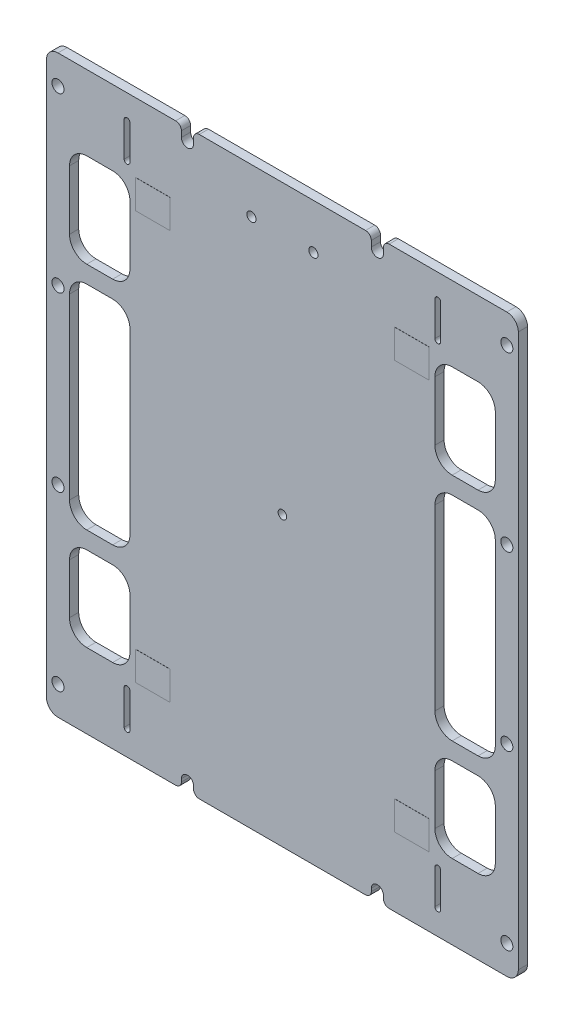
SolidWorks part; units mm, degrees
material "FR4_stuffedProtoboard"
ref_plane "Front Plane" through (0, 0, 0) normal (0, 0, 1) x (1, 0, 0)
ref_plane "Top Plane" through (0, 0, 0) normal (0, 1, 0) x (1, 0, 0)
ref_plane "Right Plane" through (0, 0, 0) normal (1, 0, 0) x (0, 0, -1)
sketch "Sketch1" plane through (0, 0, 0) normal (0, 0, 1) x (1, 0, 0)
  line L1 (-39, -50) -> (39, -50)
  line L2 (-41, -48) -> (-41, 48)
  line L3 (-39, 50) -> (39, 50)
  line L4 (41, -48) -> (41, 48)
  line L5 (-41, -50) -> (41, 50) construction
  line L6 (-41, 50) -> (41, -50) construction
  arc A0 (-39, -50) -> (-41, -48) centre (-39, -48) cw
  arc A1 (39, -50) -> (41, -48) centre (39, -48) ccw
  arc A2 (39, 50) -> (41, 48) centre (39, 48) cw
  arc A3 (-41, 48) -> (-39, 50) centre (-39, 48) cw
  point P0 (0, 0)
  dimension "D3" = 2
  dimension "D1" = 100
  dimension "D2" = 82
extrude "boardOutline" add sketch "Sketch1" along normal blind 1.6
sketch "Sketch2" plane through (0, 0, 1.6) normal (0, 0, 1) x (1, 0, 0)
  line L0 (39, 50) -> (-39, 50) construction
  line L1 (-41, 48) -> (-41, -48) construction
  line L3 (-37.5, 44.2) -> (-37.5, 4.2) construction
  circle A0 centre (0, 0) radius 0.75
  circle A1 centre (-37.5, 44.2) radius 1.05 construction
  circle A2 centre (37.5, 44.2) radius 1.05 construction
  circle A3 centre (37.5, 4.2) radius 1.05 construction
  circle A4 centre (37.5, -35.8) radius 1.05 construction
  circle A5 centre (-37.5, 4.2) radius 1.05 construction
  circle A6 centre (-37.5, -35.8) radius 1.05 construction
  circle A7 centre (-5.38, 42.15) radius 0.8
  circle A8 centre (5.39, 42.15) radius 0.8
  dimension "D1" = 1.5
  dimension "D2" = 2.1
  dimension "D9" = 10.77
  dimension "D7" = 1.6
  dimension "D11" = 7.85
  dimension "D12" = 35.62
  dimension "D3" = 5.8
  dimension "D4" = 3.5
  dimension "D8" = 40
  dimension "D10" = 37.5
  dimension "D5" = 2
  dimension "D6" = 3
extrude "componentHoles" cut sketch "Sketch2" against normal through all
sketch "Sketch4" plane through (0, 0, 1.6) normal (0, 0, 1) x (1, 0, 0)
  line L0 (-27, 39.75) -> (-27, 45.75) construction
  line L1 (-27.5, 39.75) -> (-27.5, 45.75)
  line L2 (-26.5, 39.75) -> (-26.5, 45.75)
  line L3 (39, 50) -> (-39, 50) construction
  line L4 (-41, 48) -> (-41, -48) construction
  line L5 (27, 39.75) -> (27, 45.75) construction
  line L6 (26.5, 39.75) -> (26.5, 45.75)
  line L7 (27.5, 39.75) -> (27.5, 45.75)
  line L8 (27, -45.75) -> (27, -39.75) construction
  line L9 (26.5, -45.75) -> (26.5, -39.75)
  line L10 (27.5, -45.75) -> (27.5, -39.75)
  line L11 (-27, -45.75) -> (-27, -39.75) construction
  line L12 (-27.5, -45.75) -> (-27.5, -39.75)
  line L13 (-26.5, -45.75) -> (-26.5, -39.75)
  line L14 (-27, 39.75) -> (27, 39.75) construction
  line L15 (-39, -50) -> (39, -50) construction
  arc A0 (-27.5, 39.75) -> (-26.5, 39.75) centre (-27, 39.75) ccw
  arc A1 (-26.5, 45.75) -> (-27.5, 45.75) centre (-27, 45.75) ccw
  arc A2 (26.5, 39.75) -> (27.5, 39.75) centre (27, 39.75) ccw
  arc A3 (27.5, 45.75) -> (26.5, 45.75) centre (27, 45.75) ccw
  arc A4 (26.5, -45.75) -> (27.5, -45.75) centre (27, -45.75) ccw
  arc A5 (27.5, -39.75) -> (26.5, -39.75) centre (27, -39.75) ccw
  arc A6 (-27.5, -45.75) -> (-26.5, -45.75) centre (-27, -45.75) ccw
  arc A7 (-26.5, -39.75) -> (-27.5, -39.75) centre (-27, -39.75) ccw
  point P2 (-27, 42.75)
  point P16 (27, 42.75)
  point P23 (27, -42.75)
  point P30 (-27, -42.75)
  dimension "D1" = 4.25
  dimension "D2" = 13.5
  dimension "D3" = 1
  dimension "D4" = 6
  dimension "D7" = 54
  dimension "D8" = 14
  dimension "D9" = 4.25
  dimension "D10" = 4.25
  dimension "D5" = 2
  dimension "D6" = 2
extrude "solarCellContactHoles" cut sketch "Sketch4" against normal blind 1.6
sketch "Sketch3" plane through (0, 0, 1.6) normal (0, 0, 1) x (1, 0, 0)
  line L1 (-34, 37) -> (-29.5, 37)
  line L2 (-37, 34) -> (-37, 23.7)
  line L3 (-34, 20.7) -> (-29.5, 20.7)
  line L4 (-26.5, 34) -> (-26.5, 23.7)
  line L5 (-41, 48) -> (-41, -48) construction
  line L6 (-29.5, -22.3) -> (-34, -22.3)
  line L9 (0, 50) -> (0, -50) construction
  line L10 (39, 50) -> (-39, 50) construction
  line L11 (-39, -50) -> (39, -50) construction
  line L12 (-26.5, -25.3) -> (-26.5, -34)
  line L13 (-29.5, -37) -> (-34, -37)
  line L14 (-37, -25.3) -> (-37, -34)
  line L19 (-29.5, -19.3) -> (-34, -19.3)
  line L25 (-26.5, -16.3) -> (-26.5, 14.7)
  line L26 (-29.5, 17.7) -> (-34, 17.7)
  line L27 (-37, -16.3) -> (-37, 14.7)
  arc A0 (-37, 23.7) -> (-34, 20.7) centre (-34, 23.7) ccw
  arc A1 (-29.5, 20.7) -> (-26.5, 23.7) centre (-29.5, 23.7) ccw
  arc A2 (-29.5, 37) -> (-26.5, 34) centre (-29.5, 34) cw
  arc A3 (-34, 37) -> (-37, 34) centre (-34, 34) ccw
  arc A4 (-29.5, -19.3) -> (-26.5, -16.3) centre (-29.5, -16.3) ccw
  arc A5 (-26.5, -34) -> (-29.5, -37) centre (-29.5, -34) cw
  arc A6 (-34, -37) -> (-37, -34) centre (-34, -34) cw
  arc A7 (-34, -22.3) -> (-37, -25.3) centre (-34, -25.3) ccw
  arc A8 (-29.5, -22.3) -> (-26.5, -25.3) centre (-29.5, -25.3) cw
  arc A17 (-34, -19.3) -> (-37, -16.3) centre (-34, -16.3) cw
  arc A18 (-34, 17.7) -> (-37, 14.7) centre (-34, 14.7) ccw
  arc A19 (-26.5, 14.7) -> (-29.5, 17.7) centre (-29.5, 14.7) ccw
  point P12 (-26.5, 20.7)
  point P15 (-26.5, 37)
  point P18 (-37, 37)
  dimension "D5" = 3
  dimension "D10" = 13
  dimension "D7" = 3
  dimension "D11" = 3
  dimension "D1" = 10.5
  dimension "D2" = 29.3
  dimension "D3" = 13
  dimension "D4" = 4
  dimension "D8" = 3
  dimension "D9" = 3
  dimension "D6" = 37
extrude "windows_1side" cut sketch "Sketch3" against normal through all
sketch "Sketch5" plane through (0, 0, 1.6) normal (0, 0, 1) x (1, 0, 0)
  line L0 (-41, 48) -> (-41, -48) construction
  line L1 (-25.5, 38) -> (-19.5, 38)
  line L2 (-25.5, 38) -> (-25.5, 33)
  line L3 (-25.5, 33) -> (-19.5, 33)
  line L4 (-19.5, 38) -> (-19.5, 33)
  line L5 (39, 50) -> (-39, 50) construction
  line L6 (19.5, 38) -> (19.5, 33)
  line L7 (25.5, 38) -> (25.5, 33)
  line L8 (19.5, 33) -> (25.5, 33)
  line L9 (19.5, 38) -> (25.5, 38)
  line L10 (19.5, -33) -> (19.5, -38)
  line L11 (25.5, -33) -> (25.5, -38)
  line L12 (19.5, -38) -> (25.5, -38)
  line L13 (19.5, -33) -> (25.5, -33)
  line L14 (-25.5, -33) -> (-25.5, -38)
  line L15 (-19.5, -33) -> (-19.5, -38)
  line L16 (-25.5, -38) -> (-19.5, -38)
  line L17 (-25.5, -33) -> (-19.5, -33)
  line L18 (-25.5, 38) -> (19.5, 38) construction
  line L19 (-25.5, 38) -> (-25.5, -33) construction
  dimension "D1" = 5
  dimension "D2" = 6
  dimension "D3" = 15.5
  dimension "D4" = 12
  dimension "D7" = 45
  dimension "D8" = 71
  dimension "D5" = 2
  dimension "D6" = 2
extrude "contactPads" add sketch "Sketch5" along normal blind 0.02
hole_wizard "M2 Clearance Hole1" positions "Sketch6" profile "Sketch7" hole size "M2" standard "ANSI Metric" end condition through all
sketch "Sketch6" plane through (0, 0, 0) normal (0, 0, -1) x (-1, 0, 0)
  line L5 (39, -50) -> (39, -45) construction
  line L6 (39, -50) -> (-39, -50) construction
  line L7 (39, -45) -> (39, -15) construction
  line L8 (39, -15) -> (39, 15) construction
  line L9 (39, 15) -> (39, 45) construction
  line L10 (39, 45) -> (39, 50) construction
  line L11 (-39, 50) -> (39, 50) construction
  line L15 (37, -27.0602) -> (41, -27.0602) construction
  line L16 (37, -25.3) -> (37, -34) construction
  line L17 (41, 48) -> (41, -48) construction
  point P0 (39, 45)
  point P27 (39, -15)
  point P36 (39, -45)
  point P38 (39, 15)
  point P73 (39, -27.0602)
  dimension "D2" = 5
sketch "Sketch7" plane through (-39, 45, 0) normal (1, 0, 0) x (0, 1, 0)
  line L0 (0, 0) -> (0, 1.62)
  line L1 (0, 1.62) -> (1.05, 1.62)
  line L2 (1.05, 1.62) -> (1.05, 0)
  line L5 (1.05, 0) -> (0, 0)
  line L11 (0, -6.35) -> (0, 107.95) construction
  dimension "Thru Hole Dia." = 2.1
  dimension "Thru Hole Depth" = 1.62
sketch "Sketch10" plane through (0, 0, 0) normal (0, 0, -1) x (-1, 0, 0)
  line L0 (16.5, 48) -> (16.5, 55.0732) construction
  line L1 (15.45, 48) -> (15.45, 55.0732)
  line L2 (17.55, 48) -> (17.55, 55.0732)
  line L3 (16.5, -48.5) -> (16.5, -55.5732) construction
  line L4 (17.55, -48.5) -> (17.55, -55.5732)
  line L5 (15.45, -48.5) -> (15.45, -55.5732)
  line L6 (41, 48) -> (41, -48) construction
  line L8 (39, -50) -> (-39, -50) construction
  line L9 (-39, 50) -> (39, 50) construction
  arc A0 (15.45, 48) -> (17.55, 48) centre (16.5, 48) ccw
  arc A1 (17.55, 55.0732) -> (15.45, 55.0732) centre (16.5, 55.0732) ccw
  arc A2 (17.55, -48.5) -> (15.45, -48.5) centre (16.5, -48.5) ccw
  arc A3 (15.45, -55.5732) -> (17.55, -55.5732) centre (16.5, -55.5732) ccw
  point P2 (16.5, 51.5366)
  point P7 (16.5, -52.0366)
  dimension "D1" = 1.05
  dimension "D2" = 24.5
  dimension "D3" = 2
  dimension "D4" = 1.5
extrude "Cut-Extrude1" cut sketch "Sketch10" against normal through all both and the other way through all
fillet "Fillet3" radius 1 4 edges at (-17.55, 50, 0.8) (-15.45, 50, 0.8) (-15.45, -50, 0.8) (-17.55, -50, 0.8)
mirror "Mirror1" about plane through (0, 0, 0) normal (1, 0, 0) of "Cut-Extrude1", "Fillet3", "windows_1side", "M2 Clearance Hole1"
sketch "thermalContact" plane through (0, 0, 1.6) normal (0, 0, 1) x (1, 0, 0)
  line L0 (-37, 43) -> (-37, 23.7) construction
  line L1 (-34, 20.7) -> (-21, 20.7) construction
  line L2 (-18, 23.7) -> (-18, 43) construction
  line L3 (-21, 46) -> (-34, 46) construction
  line L4 (-41, 48) -> (-41, -162)
  line L5 (39, 50) -> (-39, 50)
  line L6 (41, -162) -> (41, 48)
  line L7 (-39, -164) -> (39, -164)
  line L8 (-41, 48) -> (-41, -162)
  line L9 (39, 50) -> (-39, 50)
  line L10 (41, -162) -> (41, 48)
  line L11 (-39, -164) -> (39, -164)
  line L12 (-37, 43) -> (-37, 23.7)
  line L13 (-34, 20.7) -> (-21, 20.7)
  line L14 (-18, 23.7) -> (-18, 43)
  line L15 (-21, 46) -> (-34, 46)
  line L16 (18, 43) -> (18, 23.7) construction
  line L17 (21, 20.7) -> (34, 20.7) construction
  line L18 (37, 23.7) -> (37, 43) construction
  line L19 (34, 46) -> (21, 46) construction
  line L20 (18, 43) -> (18, 23.7)
  line L21 (21, 20.7) -> (34, 20.7)
  line L22 (37, 23.7) -> (37, 43)
  line L23 (34, 46) -> (21, 46)
  line L24 (-12, -47) -> (12, -47) construction
  line L25 (15, -44) -> (15, -25.3) construction
  line L26 (12, -22.3) -> (-12, -22.3) construction
  line L27 (-15, -25.3) -> (-15, -44) construction
  line L28 (-12, -47) -> (12, -47)
  line L29 (15, -44) -> (15, -25.3)
  line L30 (12, -22.3) -> (-12, -22.3)
  line L31 (-15, -25.3) -> (-15, -44)
  line L32 (-37, -25.3) -> (-37, -44) construction
  line L33 (-34, -47) -> (-21, -47) construction
  line L34 (-18, -44) -> (-18, -25.3) construction
  line L35 (-21, -22.3) -> (-34, -22.3) construction
  line L36 (-37, -25.3) -> (-37, -44)
  line L37 (-34, -47) -> (-21, -47)
  line L38 (-18, -44) -> (-18, -25.3)
  line L39 (-21, -22.3) -> (-34, -22.3)
  line L40 (18, -25.3) -> (18, -44) construction
  line L41 (21, -47) -> (34, -47) construction
  line L42 (37, -44) -> (37, -25.3) construction
  line L43 (34, -22.3) -> (21, -22.3) construction
  line L44 (18, -25.3) -> (18, -44)
  line L45 (21, -47) -> (34, -47)
  line L46 (37, -44) -> (37, -25.3)
  line L47 (34, -22.3) -> (21, -22.3)
  line L48 (-12, -19.3) -> (12, -19.3) construction
  line L49 (15, -16.3) -> (15, 14.7) construction
  line L50 (12, 17.7) -> (-12, 17.7) construction
  line L51 (-15, 14.7) -> (-15, -16.3) construction
  line L52 (-12, -19.3) -> (12, -19.3)
  line L53 (15, -16.3) -> (15, 14.7)
  line L54 (12, 17.7) -> (-12, 17.7)
  line L55 (-15, 14.7) -> (-15, -16.3)
  line L56 (-21, 17.7) -> (-34, 17.7) construction
  line L57 (-37, 14.7) -> (-37, -16.3) construction
  line L58 (-34, -19.3) -> (-21, -19.3) construction
  line L59 (-18, -16.3) -> (-18, 14.7) construction
  line L60 (-21, 17.7) -> (-34, 17.7)
  line L61 (-37, 14.7) -> (-37, -16.3)
  line L62 (-34, -19.3) -> (-21, -19.3)
  line L63 (-18, -16.3) -> (-18, 14.7)
  line L64 (21, -19.3) -> (34, -19.3) construction
  line L65 (37, -16.3) -> (37, 14.7) construction
  line L66 (34, 17.7) -> (21, 17.7) construction
  line L67 (18, 14.7) -> (18, -16.3) construction
  line L68 (21, -19.3) -> (34, -19.3)
  line L69 (37, -16.3) -> (37, 14.7)
  line L70 (34, 17.7) -> (21, 17.7)
  line L71 (18, 14.7) -> (18, -16.3)
  line L72 (-12, 20.7) -> (12, 20.7) construction
  line L73 (15, 23.7) -> (15, 43) construction
  line L74 (12, 46) -> (-12, 46) construction
  line L75 (-15, 43) -> (-15, 23.7) construction
  line L76 (-12, 20.7) -> (12, 20.7)
  line L77 (15, 23.7) -> (15, 43)
  line L78 (12, 46) -> (-12, 46)
  line L79 (-15, 43) -> (-15, 23.7)
  line L80 (-21, -50) -> (-34, -50) construction
  line L81 (-37, -53) -> (-37, -61) construction
  line L82 (-34, -64) -> (-21, -64) construction
  line L83 (-18, -61) -> (-18, -53) construction
  line L84 (-21, -50) -> (-34, -50)
  line L85 (-37, -53) -> (-37, -61)
  line L86 (-34, -64) -> (-21, -64)
  line L87 (-18, -61) -> (-18, -53)
  line L88 (-15, -53) -> (-15, -61) construction
  line L89 (-12, -64) -> (12, -64) construction
  line L90 (15, -61) -> (15, -53) construction
  line L91 (12, -50) -> (-12, -50) construction
  line L92 (-15, -53) -> (-15, -61)
  line L93 (-12, -64) -> (12, -64)
  line L94 (15, -61) -> (15, -53)
  line L95 (12, -50) -> (-12, -50)
  line L96 (18, -53) -> (18, -61) construction
  line L97 (21, -64) -> (34, -64) construction
  line L98 (37, -61) -> (37, -53) construction
  line L99 (34, -50) -> (21, -50) construction
  line L100 (18, -53) -> (18, -61)
  line L101 (21, -64) -> (34, -64)
  line L102 (37, -61) -> (37, -53)
  line L103 (34, -50) -> (21, -50)
  arc A0 (-34, 46) -> (-37, 43) centre (-34, 43) ccw construction
  arc A1 (-37, 23.7) -> (-34, 20.7) centre (-34, 23.7) ccw construction
  arc A2 (-21, 20.7) -> (-18, 23.7) centre (-21, 23.7) ccw construction
  arc A3 (-18, 43) -> (-21, 46) centre (-21, 43) ccw construction
  arc A4 (-39, 50) -> (-41, 48) centre (-39, 48) ccw
  arc A5 (41, 48) -> (39, 50) centre (39, 48) ccw
  arc A6 (39, -164) -> (41, -162) centre (39, -162) ccw
  arc A7 (-41, -162) -> (-39, -164) centre (-39, -162) ccw
  arc A8 (-39, 50) -> (-41, 48) centre (-39, 48) ccw
  arc A9 (41, 48) -> (39, 50) centre (39, 48) ccw
  arc A10 (39, -164) -> (41, -162) centre (39, -162) ccw
  arc A11 (-41, -162) -> (-39, -164) centre (-39, -162) ccw
  arc A12 (-34, 46) -> (-37, 43) centre (-34, 43) ccw
  arc A13 (-37, 23.7) -> (-34, 20.7) centre (-34, 23.7) ccw
  arc A14 (-21, 20.7) -> (-18, 23.7) centre (-21, 23.7) ccw
  arc A15 (-18, 43) -> (-21, 46) centre (-21, 43) ccw
  arc A16 (21, 46) -> (18, 43) centre (21, 43) ccw construction
  arc A17 (18, 23.7) -> (21, 20.7) centre (21, 23.7) ccw construction
  arc A18 (34, 20.7) -> (37, 23.7) centre (34, 23.7) ccw construction
  arc A19 (37, 43) -> (34, 46) centre (34, 43) ccw construction
  arc A20 (21, 46) -> (18, 43) centre (21, 43) ccw
  arc A21 (18, 23.7) -> (21, 20.7) centre (21, 23.7) ccw
  arc A22 (34, 20.7) -> (37, 23.7) centre (34, 23.7) ccw
  arc A23 (37, 43) -> (34, 46) centre (34, 43) ccw
  arc A24 (-15, -44) -> (-12, -47) centre (-12, -44) ccw construction
  arc A25 (12, -47) -> (15, -44) centre (12, -44) ccw construction
  arc A26 (15, -25.3) -> (12, -22.3) centre (12, -25.3) ccw construction
  arc A27 (-12, -22.3) -> (-15, -25.3) centre (-12, -25.3) ccw construction
  arc A28 (-15, -44) -> (-12, -47) centre (-12, -44) ccw
  arc A29 (12, -47) -> (15, -44) centre (12, -44) ccw
  arc A30 (15, -25.3) -> (12, -22.3) centre (12, -25.3) ccw
  arc A31 (-12, -22.3) -> (-15, -25.3) centre (-12, -25.3) ccw
  arc A32 (-34, -22.3) -> (-37, -25.3) centre (-34, -25.3) ccw construction
  arc A33 (-37, -44) -> (-34, -47) centre (-34, -44) ccw construction
  arc A34 (-21, -47) -> (-18, -44) centre (-21, -44) ccw construction
  arc A35 (-18, -25.3) -> (-21, -22.3) centre (-21, -25.3) ccw construction
  arc A36 (-34, -22.3) -> (-37, -25.3) centre (-34, -25.3) ccw
  arc A37 (-37, -44) -> (-34, -47) centre (-34, -44) ccw
  arc A38 (-21, -47) -> (-18, -44) centre (-21, -44) ccw
  arc A39 (-18, -25.3) -> (-21, -22.3) centre (-21, -25.3) ccw
  arc A40 (21, -22.3) -> (18, -25.3) centre (21, -25.3) ccw construction
  arc A41 (18, -44) -> (21, -47) centre (21, -44) ccw construction
  arc A42 (34, -47) -> (37, -44) centre (34, -44) ccw construction
  arc A43 (37, -25.3) -> (34, -22.3) centre (34, -25.3) ccw construction
  arc A44 (21, -22.3) -> (18, -25.3) centre (21, -25.3) ccw
  arc A45 (18, -44) -> (21, -47) centre (21, -44) ccw
  arc A46 (34, -47) -> (37, -44) centre (34, -44) ccw
  arc A47 (37, -25.3) -> (34, -22.3) centre (34, -25.3) ccw
  arc A48 (-15, -16.3) -> (-12, -19.3) centre (-12, -16.3) ccw construction
  arc A49 (12, -19.3) -> (15, -16.3) centre (12, -16.3) ccw construction
  arc A50 (15, 14.7) -> (12, 17.7) centre (12, 14.7) ccw construction
  arc A51 (-12, 17.7) -> (-15, 14.7) centre (-12, 14.7) ccw construction
  arc A52 (-15, -16.3) -> (-12, -19.3) centre (-12, -16.3) ccw
  arc A53 (12, -19.3) -> (15, -16.3) centre (12, -16.3) ccw
  arc A54 (15, 14.7) -> (12, 17.7) centre (12, 14.7) ccw
  arc A55 (-12, 17.7) -> (-15, 14.7) centre (-12, 14.7) ccw
  arc A56 (-18, 14.7) -> (-21, 17.7) centre (-21, 14.7) ccw construction
  arc A57 (-34, 17.7) -> (-37, 14.7) centre (-34, 14.7) ccw construction
  arc A58 (-37, -16.3) -> (-34, -19.3) centre (-34, -16.3) ccw construction
  arc A59 (-21, -19.3) -> (-18, -16.3) centre (-21, -16.3) ccw construction
  arc A60 (-18, 14.7) -> (-21, 17.7) centre (-21, 14.7) ccw
  arc A61 (-34, 17.7) -> (-37, 14.7) centre (-34, 14.7) ccw
  arc A62 (-37, -16.3) -> (-34, -19.3) centre (-34, -16.3) ccw
  arc A63 (-21, -19.3) -> (-18, -16.3) centre (-21, -16.3) ccw
  arc A64 (18, -16.3) -> (21, -19.3) centre (21, -16.3) ccw construction
  arc A65 (34, -19.3) -> (37, -16.3) centre (34, -16.3) ccw construction
  arc A66 (37, 14.7) -> (34, 17.7) centre (34, 14.7) ccw construction
  arc A67 (21, 17.7) -> (18, 14.7) centre (21, 14.7) ccw construction
  arc A68 (18, -16.3) -> (21, -19.3) centre (21, -16.3) ccw
  arc A69 (34, -19.3) -> (37, -16.3) centre (34, -16.3) ccw
  arc A70 (37, 14.7) -> (34, 17.7) centre (34, 14.7) ccw
  arc A71 (21, 17.7) -> (18, 14.7) centre (21, 14.7) ccw
  arc A72 (-15, 23.7) -> (-12, 20.7) centre (-12, 23.7) ccw construction
  arc A73 (12, 20.7) -> (15, 23.7) centre (12, 23.7) ccw construction
  arc A74 (15, 43) -> (12, 46) centre (12, 43) ccw construction
  arc A75 (-12, 46) -> (-15, 43) centre (-12, 43) ccw construction
  arc A76 (-15, 23.7) -> (-12, 20.7) centre (-12, 23.7) ccw
  arc A77 (12, 20.7) -> (15, 23.7) centre (12, 23.7) ccw
  arc A78 (15, 43) -> (12, 46) centre (12, 43) ccw
  arc A79 (-12, 46) -> (-15, 43) centre (-12, 43) ccw
  arc A80 (-34, -50) -> (-37, -53) centre (-34, -53) ccw construction
  arc A81 (-37, -61) -> (-34, -64) centre (-34, -61) ccw construction
  arc A82 (-21, -64) -> (-18, -61) centre (-21, -61) ccw construction
  arc A83 (-18, -53) -> (-21, -50) centre (-21, -53) ccw construction
  arc A84 (-34, -50) -> (-37, -53) centre (-34, -53) ccw
  arc A85 (-37, -61) -> (-34, -64) centre (-34, -61) ccw
  arc A86 (-21, -64) -> (-18, -61) centre (-21, -61) ccw
  arc A87 (-18, -53) -> (-21, -50) centre (-21, -53) ccw
  arc A88 (-15, -61) -> (-12, -64) centre (-12, -61) ccw construction
  arc A89 (12, -64) -> (15, -61) centre (12, -61) ccw construction
  arc A90 (15, -53) -> (12, -50) centre (12, -53) ccw construction
  arc A91 (-12, -50) -> (-15, -53) centre (-12, -53) ccw construction
  arc A92 (-15, -61) -> (-12, -64) centre (-12, -61) ccw
  arc A93 (12, -64) -> (15, -61) centre (12, -61) ccw
  arc A94 (15, -53) -> (12, -50) centre (12, -53) ccw
  arc A95 (-12, -50) -> (-15, -53) centre (-12, -53) ccw
  arc A96 (21, -50) -> (18, -53) centre (21, -53) ccw construction
  arc A97 (18, -61) -> (21, -64) centre (21, -61) ccw construction
  arc A98 (34, -64) -> (37, -61) centre (34, -61) ccw construction
  arc A99 (37, -53) -> (34, -50) centre (34, -53) ccw construction
  arc A100 (18, -61) -> (21, -64) centre (21, -61) ccw
  arc A101 (34, -64) -> (37, -61) centre (34, -61) ccw
  arc A102 (37, -53) -> (34, -50) centre (34, -53) ccw
  arc A103 (21, -50) -> (18, -53) centre (21, -53) ccw
  dimension "D1" = 0
